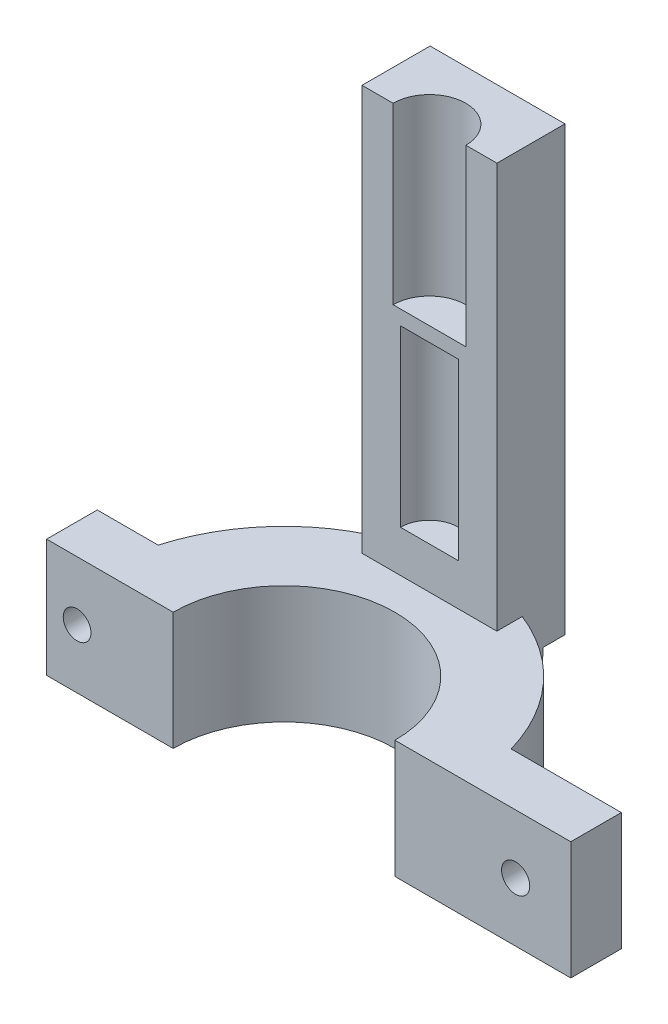
SolidWorks part; units mm, degrees
ref_plane "前基準面" through (0, 0, 0) normal (0, 0, 1) x (1, 0, 0)
ref_plane "上基準面" through (0, 0, 0) normal (0, 1, 0) x (1, 0, 0)
ref_plane "右基準面" through (0, 0, 0) normal (1, 0, 0) x (0, 0, -1)
sketch "草圖1" plane through (0, 0, 0) normal (0, 1, 0) x (1, 0, 0)
  line L1 (-15.75, 7.075) -> (15.75, 7.075)
  line L2 (-15.75, 7.075) -> (-15.75, -7.075)
  line L3 (-15.75, -7.075) -> (15.75, -7.075)
  line L4 (15.75, 7.075) -> (15.75, -7.075)
  line L5 (-15.75, 7.075) -> (15.75, -7.075) construction
  line L6 (-15.75, -7.075) -> (15.75, 7.075) construction
  point P0 (0, 0)
  dimension "D1" = 14.15
  dimension "D2" = 31.5
extrude "伸長-薄件1" add sketch "草圖1" along normal blind 12.25 thin thin type one direction wall 10
sketch "草圖2" plane through (0, 12.25, 0) normal (0, 1, 0) x (1, 0, 0)
  line L0 (-1014.255, 0) -> (48985.745, 0) construction
  line L1 (-15.75, 7.075) -> (-15.75, -7.075) construction
  line L2 (-20.75, -988.4004) -> (-20.75, 49011.5996) construction
  line L3 (-25.75, 17.075) -> (-20.75, 17.075) construction
  line L4 (-25.75, 17.075) -> (-25.75, 11.5996) construction
  line L5 (-25.75, 11.5996) -> (-20.75, 11.5996) construction
  line L6 (-20.75, 17.075) -> (-20.75, 11.5996) construction
  line L7 (25.75, 17.075) -> (20.75, 17.075) construction
  line L8 (25.75, 17.075) -> (25.75, 12.4477) construction
  line L9 (25.75, 12.4477) -> (20.75, 12.4477) construction
  line L10 (20.75, 17.075) -> (20.75, 12.4477) construction
  line L11 (20.75, -987.5523) -> (20.75, 49012.4477) construction
  circle A0 centre (-20.75, 0) radius 1.91
  circle A1 centre (20.75, 0) radius 1.91
  point P5 (-15.75, 0)
  dimension "D3" = 3.82
  dimension "D4" = 3.82
  dimension "D1" = 5
  dimension "D2" = 5
extrude "除料-伸長1" cut sketch "草圖2" against normal through all
sketch "草圖4" plane through (0, 0, 0) normal (0, -1, 0) x (1, 0, 0)
  line L0 (-1000, 0) -> (49000, 0) construction
  line L1 (25.75, 17.075) -> (25.75, -17.075) construction
  line L2 (12.75, 6.955) -> (25.75, 6.955)
  line L3 (12.75, 6.955) -> (12.75, -6.955)
  line L4 (12.75, -6.955) -> (25.75, -6.955)
  line L5 (25.75, 6.955) -> (25.75, -6.955)
  line L6 (12.75, 6.955) -> (25.75, -6.955) construction
  line L7 (12.75, -6.955) -> (25.75, 6.955) construction
  point P1 (19.25, 0)
  dimension "D1" = 13.91
  dimension "D2" = 13
extrude "填料-伸長1" add sketch "草圖4" along normal blind 74.82
sketch "草圖5" plane through (12.75, 0, 0) normal (-1, 0, 0) x (0, 0, 1)
  line L0 (6.955, -74.82) -> (6.955, 0) construction
  line L1 (-6.955, -74.82) -> (6.955, -74.82)
  line L2 (-6.955, -74.82) -> (-6.955, -58.59)
  line L3 (-6.955, -58.59) -> (6.955, -58.59)
  line L4 (6.955, -74.82) -> (6.955, -58.59)
  dimension "D1" = 16.23
extrude "填料-伸長2" add sketch "草圖5" along normal blind 16
sketch "草圖7" plane through (3.6267, -74.82, 0) normal (0, -1, 0) x (1, 0, 0)
  circle A0 centre (-30.9782, 0) radius 15.25
  dimension "D1" = 30.5
extrude "伸長-薄件2" add sketch "草圖7" against normal blind 16.23 thin thin type one direction wall 10
ref_plane "平面1" through (-60, 0, 0) normal (1, 0, 0) x (0, 0, -1)
ref_plane "平面2" through (-55, 0, 0) normal (1, 0, 0) x (0, 0, -1)
ref_plane "平面3" through (-60, 0, 0) normal (1, 0, 0) x (0, 0, -1)
ref_plane "平面4" through (-60, 0, 0) normal (1, 0, 0) x (0, 0, -1)
sketch "草圖16" plane through (-60, 0, 0) normal (1, 0, 0) x (0, 0, -1)
  line L1 (6.955, -58.59) -> (-6.955, -58.59)
  line L2 (6.955, -58.59) -> (6.955, -74.82)
  line L3 (6.955, -74.82) -> (-6.955, -74.82)
  line L4 (-6.955, -58.59) -> (-6.955, -74.82)
extrude "填料-伸長4" add sketch "草圖16" along normal blind 10
sketch "草圖17" plane through (0, 0, -6.955) normal (0, 0, -1) x (-1, 0, 0)
  line L0 (-948.3753, -66.705) -> (49051.6247, -66.705) construction
  line L1 (51.6247, -74.82) -> (51.6247, -58.59) construction
  line L2 (55.8124, -1058.59) -> (55.8124, 48941.41) construction
  line L3 (51.6247, -58.59) -> (60, -58.59) construction
  circle A0 centre (55.8124, -66.705) radius 1.91
  point P5 (51.6247, -66.705)
  point P10 (55.8124, -58.59)
  dimension "D1" = 3.82
extrude "除料-伸長7" cut sketch "草圖17" against normal through all
sketch "草圖19" plane through (0, -58.59, 0) normal (0, 1, 0) x (1, 0, 0)
  line L0 (-60, 6.955) -> (-60, -6.955) construction
  line L1 (-60, 0) -> (36.5445, 0)
  line L2 (-60, 0) -> (-60, -28.4267)
  line L3 (-60, -28.4267) -> (36.5445, -28.4267)
  line L4 (36.5445, 0) -> (36.5445, -28.4267)
extrude "除料-伸長8" cut sketch "草圖19" against normal blind 41 and the other way blind 83
sketch "草圖21" plane through (25.75, 0, 0) normal (1, 0, 0) x (0, 0, -1)
  line L0 (0, -74.82) -> (0, 12.25) construction
  line L1 (0, -36.2363) -> (18.5662, -36.2363)
  line L2 (0, -36.2363) -> (0, 14.4577)
  line L3 (0, 14.4577) -> (18.5662, 14.4577)
  line L4 (18.5662, -36.2363) -> (18.5662, 14.4577)
extrude "除料-伸長10" cut sketch "草圖21" against normal blind 57
sketch "草圖22" plane through (0, -36.2363, 0) normal (0, 1, 0) x (1, 0, 0)
  line L1 (12.75, 0) -> (25.75, 0)
  line L2 (12.75, 0) -> (12.75, 6.955)
  line L3 (12.75, 6.955) -> (25.75, 6.955)
  line L4 (25.75, 0) -> (25.75, 6.955)
extrude "除料-伸長11" cut sketch "草圖22" against normal blind 57
ref_plane "平面5" through (0, 0, -30) normal (0, 0, 1) x (1, 0, 0)
sketch "草圖23" plane through (0, 0, -30) normal (0, 0, 1) x (1, 0, 0)
  line L0 (-27.3515, -1058.59) -> (-27.3515, 48941.41) construction
  line L1 (-3.0782, -58.59) -> (-51.6247, -58.59) construction
  line L2 (-3.0782, -74.82) -> (-3.0782, -58.59) construction
  line L3 (-18.0782, -28.8448) -> (-36.6247, -28.8448)
  line L4 (-18.0782, -28.8448) -> (-18.0782, -71.3448)
  line L5 (-18.0782, -71.3448) -> (-36.6247, -71.3448)
  line L6 (-36.6247, -28.8448) -> (-36.6247, -71.3448)
  line L7 (-51.6247, -74.82) -> (-51.6247, -58.59) construction
  point P5 (-27.3515, -58.59)
  dimension "D1" = 15
  dimension "D2" = 15
  dimension "D3" = 42.5
extrude "填料-伸長6" add sketch "草圖23" along normal blind 10 and the other way blind 5
sketch "草圖24" plane through (0, -28.8448, 0) normal (0, 1, 0) x (1, 0, 0)
  line L0 (-18.0782, 20) -> (-36.6247, 20) construction
  circle A0 centre (-27.3515, 20) radius 4
  dimension "D1" = 8
extrude "除料-伸長12" cut sketch "草圖24" against normal blind 24
sketch "草圖26" plane through (0, -28.8448, 0) normal (0, 1, 0) x (1, 0, 0)
  line L0 (-36.6247, 35) -> (-36.6247, 20) construction
  line L1 (-18.0782, 35) -> (-36.6247, 35)
  line L2 (-18.0782, 35) -> (-18.0782, 26.3584)
  line L3 (-18.0782, 26.3584) -> (-36.6247, 26.3584)
  line L4 (-36.6247, 35) -> (-36.6247, 26.3584)
extrude "除料-伸長13" cut sketch "草圖26" against normal through all
fillet "圓角1" radius 10 1 edges at (-27.3515, -71.3448, -26.3584)
sketch "草圖27" plane through (0, 0, -6.955) normal (0, 0, -1) x (-1, 0, 0)
  line L0 (3.0782, -74.82) -> (-12.75, -74.82) construction
  line L1 (-12.75, -58.59) -> (-12.08, -58.59)
  line L2 (-12.75, -58.59) -> (-12.75, -74.82)
  line L3 (-12.75, -74.82) -> (-12.08, -74.82)
  line L4 (-12.08, -58.59) -> (-12.08, -74.82)
  dimension "D1" = 0.67
extrude "除料-伸長14" cut sketch "草圖27" against normal blind 10
sketch "草圖28" plane through (0, -28.8448, 0) normal (0, 1, 0) x (1, 0, 0)
  line L1 (-18.0782, 20) -> (-36.6247, 20)
  line L2 (-18.0782, 20) -> (-18.0782, 26.3584)
  line L3 (-18.0782, 26.3584) -> (-36.6247, 26.3584)
  line L4 (-36.6247, 20) -> (-36.6247, 26.3584)
extrude "填料-伸長7" add sketch "草圖28" along normal blind 26
sketch "草圖29" plane through (0, -2.8448, 0) normal (0, 1, 0) x (1, 0, 0)
  line L0 (-36.6247, 20) -> (-18.0782, 20) construction
  circle A0 centre (-27.3515, 20) radius 4
  dimension "D1" = 8
extrude "除料-伸長15" cut sketch "草圖29" against normal blind 24
sketch "草圖30" plane through (0, 0, -6.955) normal (0, 0, -1) x (-1, 0, 0)
  line L0 (-4.5009, -1058.59) -> (-4.5009, 48941.41) construction
  line L1 (3.0782, -58.59) -> (-12.08, -58.59) construction
  line L2 (-1012.08, -66.705) -> (48987.92, -66.705) construction
  line L3 (-12.08, -74.82) -> (-12.08, -58.59) construction
  circle A0 centre (-4.5009, -66.705) radius 1.94
  point P5 (-4.5009, -58.59)
  point P10 (-12.08, -66.705)
  dimension "D1" = 3.88
extrude "除料-伸長16" cut sketch "草圖30" against normal blind 24
sketch "草圖31" plane through (0, -26.8448, 0) normal (0, 1, 0) x (1, 0, 0)
  line L0 (-31.3515, 20) -> (-23.3515, 20) construction
  circle A0 centre (-27.3515, 20) radius 5
  dimension "D1" = 10
extrude "除料-伸長17" cut sketch "草圖31" along normal through all
sketch "草圖32" plane through (0, 0, -26.3584) normal (0, 0, -1) x (-1, 0, 0)
  line L1 (18.0782, -2.8448) -> (36.6247, -2.8448)
  line L2 (18.0782, -2.8448) -> (18.0782, -63.6996)
  line L3 (18.0782, -63.6996) -> (36.6247, -63.6996)
  line L4 (36.6247, -2.8448) -> (36.6247, -63.6996)
extrude "填料-伸長8" add sketch "草圖32" along normal blind 5
sketch "草圖35" plane through (0, -2.8448, 0) normal (0, 1, 0) x (1, 0, 0)
  line L0 (-36.6247, 31.3584) -> (-36.6247, 20) construction
  line L1 (-18.0782, 31.3584) -> (-36.6247, 31.3584)
  line L2 (-18.0782, 31.3584) -> (-18.0782, 29.3584)
  line L3 (-18.0782, 29.3584) -> (-36.6247, 29.3584)
  line L4 (-36.6247, 31.3584) -> (-36.6247, 29.3584)
  dimension "D1" = 2
extrude "除料-伸長18" cut sketch "草圖35" against normal blind 100
